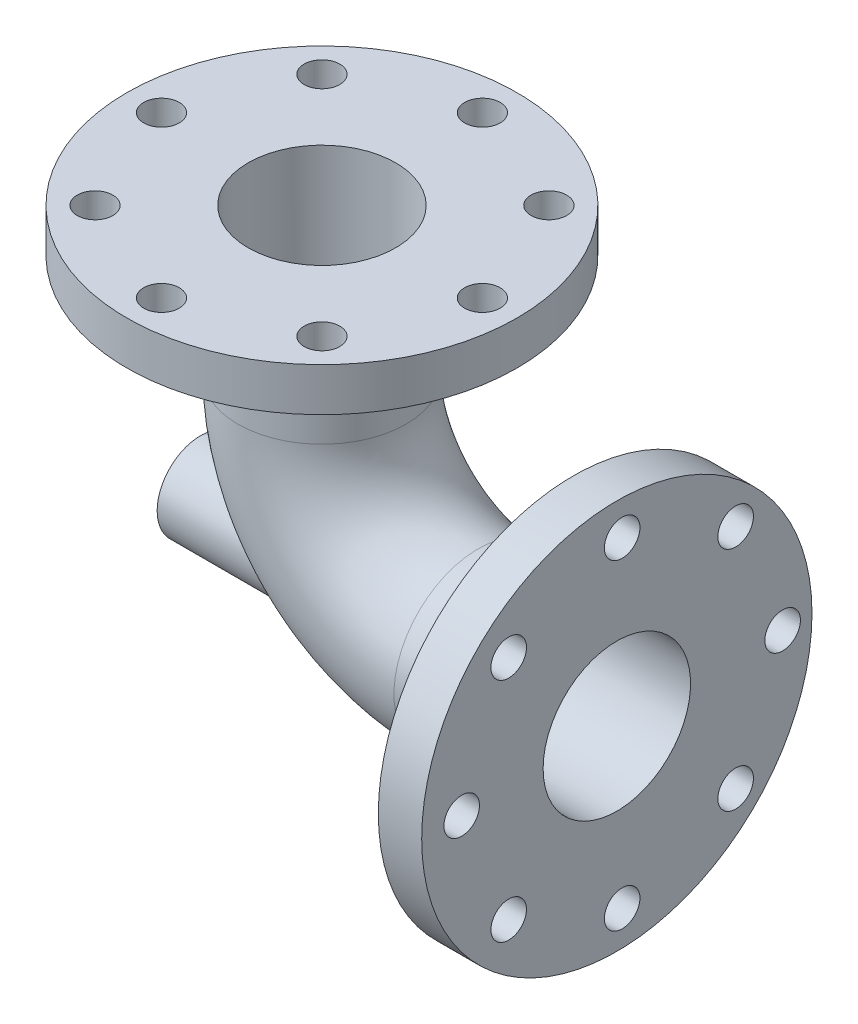
SolidWorks part; units mm, degrees
material "AISI 4340 Steel, normalized"
ref_plane "Front Plane" through (0, 0, 0) normal (0, 0, 1) x (1, 0, 0)
ref_plane "Top Plane" through (0, 0, 0) normal (0, 1, 0) x (1, 0, 0)
ref_plane "Right Plane" through (0, 0, 0) normal (1, 0, 0) x (0, 0, -1)
sketch "Sketch2" plane through (0, 0, 0) normal (0, 0, 1) x (1, 0, 0)
  line L0 (0, 175) -> (0, 90)
  line L1 (90, 0) -> (170, 0)
  arc A0 (0, 90) -> (90, 0) centre (90, 90) ccw
  point P5 (0, 0)
  point P7 (73.3963, 0)
  dimension "D3" = 90
  dimension "D1" = 170
  dimension "D2" = 175
sweep "Sweep1" add path "Sketch2" circular profile diameter 97 parameters "D3"=97
sketch "Sketch25" plane through (0, 175, 0) normal (0, 1, 0) x (1, 0, 0)
  circle A0 centre (0, 0) radius 112.5
  dimension "D1" = 225
extrude "Boss-Extrude1" add sketch "Sketch25" against normal blind 25
sketch "Sketch26" plane through (170, 0, 0) normal (1, 0, 0) x (0, 0, -1)
  circle A0 centre (0, 0) radius 112.5
  dimension "D1" = 225
extrude "Boss-Extrude2" add sketch "Sketch26" against normal blind 25
sketch "Sketch27" plane through (0, 0, 0) normal (0, 1, 0) x (1, 0, 0)
  line L0 (170, 0) -> (-70, 0)
  line L1 (170, -112.5) -> (170, 112.5) construction
  dimension "D1" = 240
sweep "Sweep2" add path "Sketch27" circular profile diameter 50 parameters "D3"=50
sweep "Cut-Sweep2" cut path "Sketch2<2>" circular profile diameter 85 parameters "D3"=85
sketch "Sketch2<2>" plane through (0, 0, 0) normal (0, 0, 1) x (1, 0, 0) same geometry as "Sketch2"
sweep "Cut-Sweep3" cut path "Sketch27<4>" circular profile diameter 18 parameters "D3"=18
sketch "Sketch27<4>" plane through (0, 0, 0) normal (0, 1, 0) x (1, 0, 0) same geometry as "Sketch27"
sketch "Sketch48" plane through (-70, 0, 0) normal (-1, 0, 0) x (0, 0, 1)
  circle A0 centre (0, 0) radius 12
  dimension "D1" = 24
extrude "Cut-Extrude1" cut sketch "Sketch48" against normal blind 12 contours A0
sketch "Sketch55" plane through (0, 175, 0) normal (0, 1, 0) x (1, 0, 0)
  circle A0 centre (-92.5, 0) radius 10.25
  circle A1 centre (-65.4074, 65.4074) radius 10.25
  circle A2 centre (0, 92.5) radius 10.25
  circle A3 centre (65.4074, 65.4074) radius 10.25
  circle A4 centre (92.5, 0) radius 10.25
  circle A5 centre (65.4074, -65.4074) radius 10.25
  circle A6 centre (0, -92.5) radius 10.25
  circle A7 centre (-65.4074, -65.4074) radius 10.25
  point P20 (0, 0)
  dimension "D1" = 20.5
  dimension "D2" = 92.5
  dimension "D3" = 8
extrude "Cut-Extrude2" cut sketch "Sketch55" against normal up to next
sketch "Sketch56" plane through (170, 0, 0) normal (1, 0, 0) x (0, 0, -1)
  circle A0 centre (-89.4282, 0) radius 10.25
  circle A1 centre (-62.3355, 65.4074) radius 10.25
  circle A2 centre (3.0718, 92.5) radius 10.25
  circle A3 centre (68.4792, 65.4074) radius 10.25
  circle A4 centre (95.5718, 0) radius 10.25
  circle A5 centre (68.4792, -65.4074) radius 10.25
  circle A6 centre (3.0718, -92.5) radius 10.25
  circle A7 centre (-62.3355, -65.4074) radius 10.25
  point P20 (3.0718, 0)
  dimension "D1" = 20.5
  dimension "D2" = 8
extrude "Cut-Extrude3" cut sketch "Sketch56" against normal up to next
